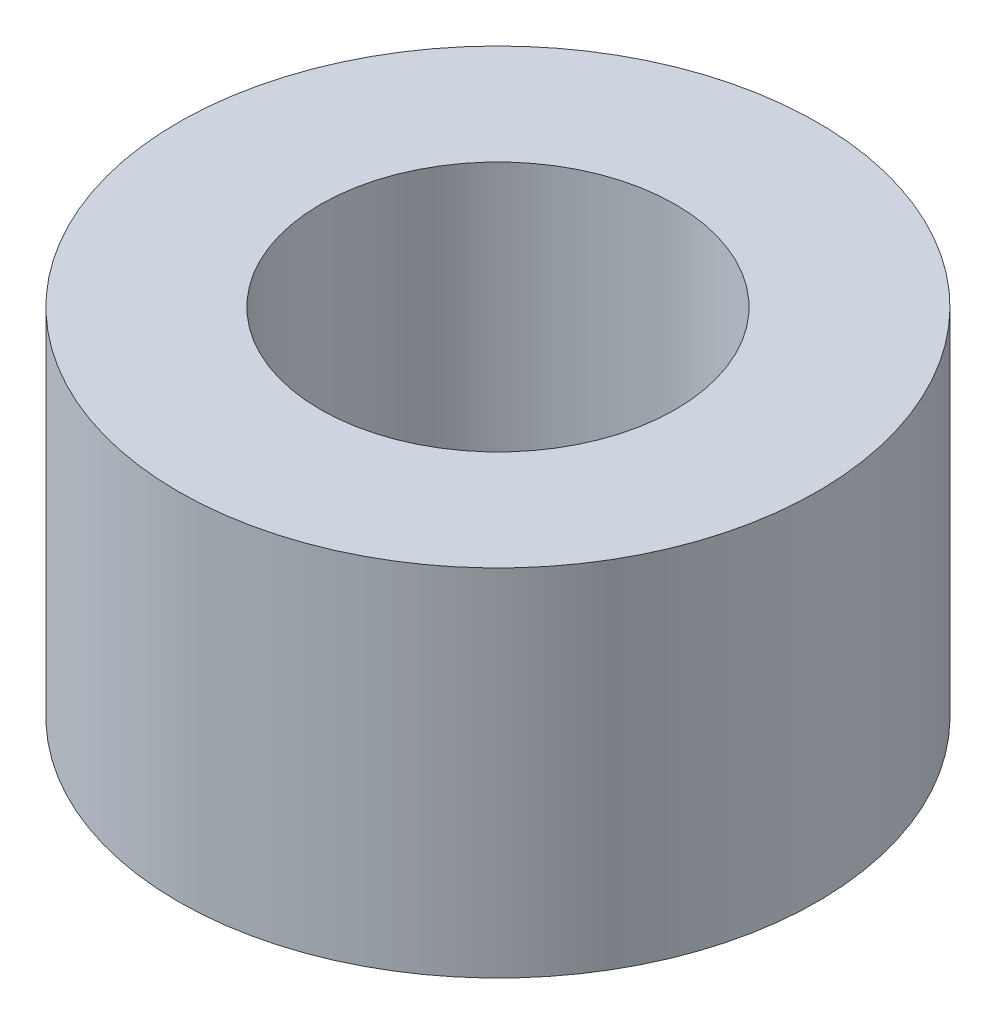
SolidWorks part; units mm, degrees
ref_plane "Front Plane" through (0, 0, 0) normal (0, 0, 1) x (1, 0, 0)
ref_plane "Top Plane" through (0, 0, 0) normal (0, 1, 0) x (1, 0, 0)
ref_plane "Right Plane" through (0, 0, 0) normal (1, 0, 0) x (0, 0, -1)
sketch "Sketch1" plane through (0, 0, 0) normal (0, 0, 1) x (1, 0, 0)
  line L0 (0, 9.4091) -> (0, -5.8636) construction
  line L2 (-2.5, -2.5) -> (-4.5, -2.5)
  line L3 (-2.5, -2.5) -> (-2.5, 2.5)
  line L4 (-2.5, 2.5) -> (-4.5, 2.5)
  line L5 (-4.5, -2.5) -> (-4.5, 2.5)
  line L6 (-2.5, -2.5) -> (-4.5, 2.5) construction
  line L7 (-2.5, 2.5) -> (-4.5, -2.5) construction
  point P3 (-3.5, 0)
  dimension "D1" = 2
  dimension "D2" = 5
  dimension "D3" = 2.5
revolve "Revolve1" add sketch "Sketch1" angle 360 about L0
